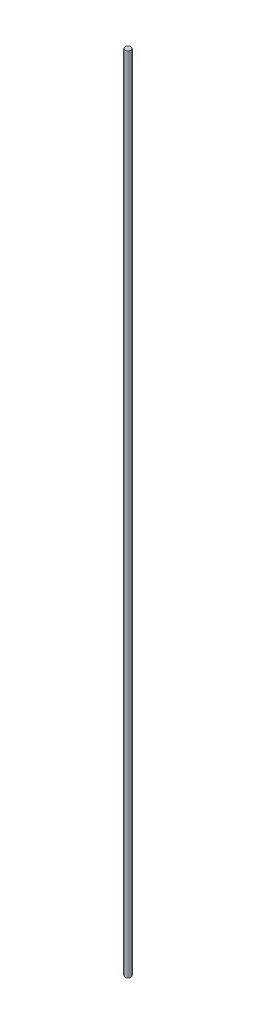
SolidWorks part; units mm, degrees
ref_plane "Front Plane" through (0, 0, 0) normal (0, 0, 1) x (1, 0, 0)
ref_plane "Top Plane" through (0, 0, 0) normal (0, 1, 0) x (1, 0, 0)
ref_plane "Right Plane" through (0, 0, 0) normal (1, 0, 0) x (0, 0, -1)
sketch "Sketch1" plane through (0, 0, 0) normal (0, 1, 0) x (1, 0, 0)
  circle A0 centre (0, 0) radius 3
  dimension "D1" = 6
extrude "Boss-Extrude1" add sketch "Sketch1" along normal blind 800
